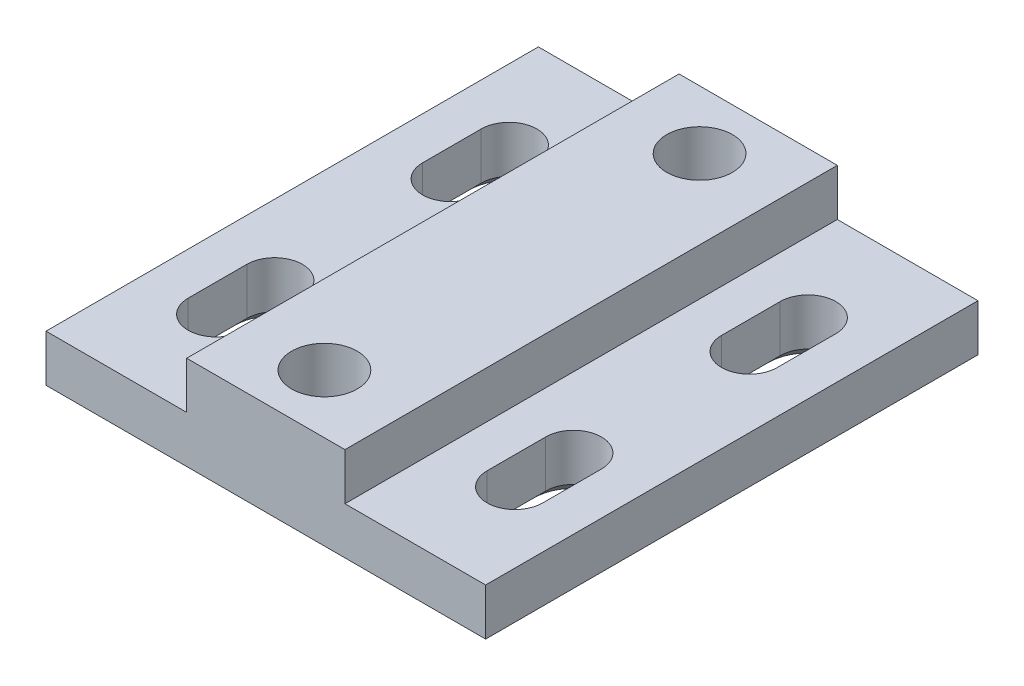
SolidWorks part; units mm, degrees
note: The reader was unsure of these and kept them because the rebuilt part matched: shared geometry of "Esboço1<3>".
ref_plane "Plano frontal" through (0, 0, 0) normal (0, 0, 1) x (1, 0, 0)
ref_plane "Plano superior" through (0, 0, 0) normal (0, 1, 0) x (1, 0, 0)
ref_plane "Plano direito" through (0, 0, 0) normal (1, 0, 0) x (0, 0, -1)
sketch "Esboço1" plane through (0, 0, 0) normal (0, 1, 0) x (1, 0, 0)
  line L0 (-12.75, 7.5) -> (-12.75, 12.5) construction
  line L1 (-18.75, 21) -> (18.75, 21)
  line L2 (-18.75, 21) -> (-18.75, -21)
  line L3 (-18.75, -21) -> (18.75, -21)
  line L4 (18.75, 21) -> (18.75, -21)
  line L5 (-18.75, 21) -> (18.75, -21) construction
  line L6 (-18.75, -21) -> (18.75, 21) construction
  line L7 (-6.75, -21) -> (6.75, -21)
  line L8 (-6.75, -21) -> (-6.75, 21)
  line L9 (-6.75, 21) -> (6.75, 21)
  line L10 (6.75, -21) -> (6.75, 21)
  line L11 (-6.75, -21) -> (6.75, 21) construction
  line L12 (-6.75, 21) -> (6.75, -21) construction
  line L13 (-15.125, 7.5) -> (-15.125, 12.5)
  line L14 (-10.375, 7.5) -> (-10.375, 12.5)
  line L15 (-12.75, -12.5) -> (-12.75, -7.5) construction
  line L16 (-15.125, -12.5) -> (-15.125, -7.5)
  line L17 (-10.375, -12.5) -> (-10.375, -7.5)
  line L18 (0, 32.4237) -> (0, -41.6464) construction
  line L19 (12.75, -12.5) -> (12.75, -7.5) construction
  line L20 (15.125, -12.5) -> (15.125, -7.5)
  line L21 (10.375, -12.5) -> (10.375, -7.5)
  line L22 (12.75, 7.5) -> (12.75, 12.5) construction
  line L23 (15.125, 7.5) -> (15.125, 12.5)
  line L24 (10.375, 7.5) -> (10.375, 12.5)
  circle A0 centre (0, 16) radius 2.8
  circle A1 centre (0, -16) radius 2.8
  arc A2 (15.125, -12.5) -> (10.375, -12.5) centre (12.75, -12.5) cw
  arc A3 (10.375, -7.5) -> (15.125, -7.5) centre (12.75, -7.5) cw
  arc A4 (-15.125, 7.5) -> (-10.375, 7.5) centre (-12.75, 7.5) ccw
  arc A5 (-15.125, -12.5) -> (-10.375, -12.5) centre (-12.75, -12.5) ccw
  arc A6 (-10.375, 12.5) -> (-15.125, 12.5) centre (-12.75, 12.5) ccw
  arc A7 (-10.375, -7.5) -> (-15.125, -7.5) centre (-12.75, -7.5) ccw
  arc A8 (15.125, 7.5) -> (10.375, 7.5) centre (12.75, 7.5) cw
  arc A9 (10.375, 12.5) -> (15.125, 12.5) centre (12.75, 12.5) cw
  point P0 (0, 0)
  point P18 (0, 0)
  point P23 (-12.75, 10)
  point P28 (-12.75, -10)
  point P33 (12.75, -10)
  point P40 (12.75, 10)
  dimension "D1" = 5.6
  dimension "D2" = 5.6
  dimension "D16" = 42
  dimension "D17" = 32
  dimension "D18" = 16
  dimension "D19" = 13.5
  dimension "D3" = 4.75
  dimension "D7" = 6
  dimension "D6" = 4.75
  dimension "D11" = 11
  dimension "D15" = 5
  dimension "D20" = 5
  dimension "D4" = 20
  dimension "D5" = 6
extrude "Ressalto-extrusão1" add sketch "Esboço1" along normal blind 5
sketch "Esboço2" plane through (0, 5, 0) normal (0, 1, 0) x (1, 0, 0)
  line L1 (5.0229, 16) -> (2.5115, 20.35)
  line L2 (2.5115, 20.35) -> (-2.5115, 20.35)
  line L3 (-2.5115, 20.35) -> (-5.0229, 16)
  line L4 (-5.0229, 16) -> (-2.5115, 11.65)
  line L5 (-2.5115, 11.65) -> (2.5115, 11.65)
  line L6 (2.5115, 11.65) -> (5.0229, 16)
  line L7 (5.0229, -16) -> (2.5115, -11.65)
  line L8 (2.5115, -11.65) -> (-2.5115, -11.65)
  line L9 (-2.5115, -11.65) -> (-5.0229, -16)
  line L10 (-5.0229, -16) -> (-2.5115, -20.35)
  line L11 (-2.5115, -20.35) -> (2.5115, -20.35)
  line L12 (2.5115, -20.35) -> (5.0229, -16)
  circle A0 centre (0, 16) radius 4.35 construction
  circle A1 centre (0, -16) radius 4.35 construction
  dimension "D1" = 8.7
  dimension "D2" = 8.7
extrude "Corte-extrusão1" cut sketch "Esboço2" along normal blind 4 from vertex
extrude "Ressalto-extrusão2" add sketch "Esboço1<3>" along normal blind 4 from vertex at 5 contours L3 L10 L1 L8 A1 A0 starting at point (-18.75, 5, 21)
sketch "Esboço1<3>" plane through (0, 0, 0) normal (0, 1, 0) x (1, 0, 0) same geometry as "Esboço1"
chamfer "Chanfro1" distance 1 angle 45 32 edges at (0, 0, 20.35) (-3.7672, 0, 18.175) (-3.7672, 0, 13.825) (0, 0, 11.65) (3.7672, 0, 13.825) (3.7672, 0, 18.175) (18.75, 0, 0) (0, 0, -21) (-18.75, 0, 0) (0, 0, 21) (0, 0, -11.65) (-3.7672, 0, -13.825) (-3.7672, 0, -18.175) (0, 0, -20.35) (3.7672, 0, -18.175) (3.7672, 0, -13.825) (12.75, 0, -14.875) (15.125, 0, -10) (12.75, 0, -5.125) (10.375, 0, -10) (12.75, 0, 5.125) (15.125, 0, 10) (12.75, 0, 14.875) (10.375, 0, 10) (-10.375, 0, -10) (-12.75, 0, -5.125) (-15.125, 0, -10) (-12.75, 0, -14.875) (-10.375, 0, 10) (-12.75, 0, 14.875) (-15.125, 0, 10) (-12.75, 0, 5.125)
equation "\"D2@Esboço1\"=\"D1@Esboço1\""
equation "\"D18@Esboço1\"=\"D17@Esboço1\"/2"
equation "\"D2@Esboço2\"=\"D1@Esboço2\""
equation "\"D6@Esboço1\"=\"D3@Esboço1\""
equation "\"D15@Esboço1\"=\"D20@Esboço1\""
equation "\"D7@Esboço1\"=\"D5@Esboço1\""
